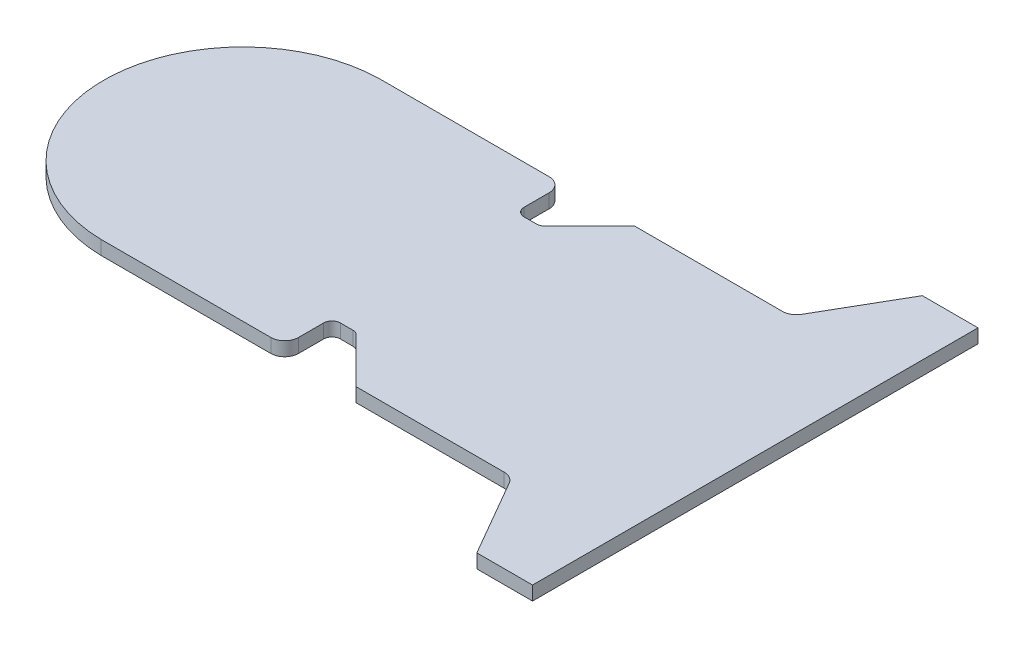
SolidWorks part; units mm, degrees
ref_plane "Front Plane" through (0, 0, 0) normal (0, 0, 1) x (1, 0, 0)
ref_plane "Top Plane" through (0, 0, 0) normal (0, 1, 0) x (1, 0, 0)
ref_plane "Right Plane" through (0, 0, 0) normal (1, 0, 0) x (0, 0, -1)
sketch "Sketch1" plane through (0, 0, 0) normal (0, 1, 0) x (1, 0, 0)
  line L0 (15.2546, 44.9902) -> (15.2546, 35.9902)
  line L1 (-50.7454, -49.9902) -> (10.2546, -49.9902)
  line L3 (-50.7454, 49.9902) -> (10.2546, 49.9902)
  line L5 (-50.7454, -49.9902) -> (50.7454, 49.9902) construction
  line L6 (-50.7454, 49.9902) -> (50.7454, -49.9902) construction
  line L7 (18.2546, 32.9902) -> (22.7119, 32.9902)
  line L8 (24.8333, 33.8689) -> (40.9546, 49.9902)
  line L9 (40.9546, 49.9902) -> (94.0678, 49.9902)
  line L10 (98.398, 52.4902) -> (114.2807, 80)
  line L11 (114.2807, 80) -> (134.2807, 80)
  line L12 (-49.7577, 0) -> (134.2807, 0) construction
  line L13 (134.2807, 80) -> (134.2807, -80)
  line L14 (40.9546, 49.9902) -> (96.9546, 49.9902)
  line L15 (40.9546, 49.9902) -> (50.7454, 49.9902)
  line L17 (114.2807, -80) -> (134.2807, -80)
  line L18 (98.398, -52.4902) -> (114.2807, -80)
  line L19 (40.9546, -49.9902) -> (94.0678, -49.9902)
  line L20 (18.2546, -32.9902) -> (22.7119, -32.9902)
  line L21 (24.8333, -33.8689) -> (40.9546, -49.9902)
  line L22 (15.2546, -44.9902) -> (15.2546, -35.9902)
  line L23 (40.9546, -49.9902) -> (50.7454, -49.9902)
  arc A0 (-50.7454, 49.9902) -> (-50.7454, -49.9902) centre (-49.7577, 0) ccw
  arc A1 (22.7119, 32.9902) -> (24.8333, 33.8689) centre (22.7119, 35.9902) ccw
  arc A2 (18.2546, 32.9902) -> (15.2546, 35.9902) centre (18.2546, 35.9902) cw
  arc A3 (15.2546, 44.9902) -> (10.2546, 49.9902) centre (10.2546, 44.9902) ccw
  arc A4 (15.2546, -44.9902) -> (10.2546, -49.9902) centre (10.2546, -44.9902) cw
  arc A5 (22.7119, -32.9902) -> (24.8333, -33.8689) centre (22.7119, -35.9902) cw
  arc A6 (18.2546, -32.9902) -> (15.2546, -35.9902) centre (18.2546, -35.9902) ccw
  arc A7 (98.398, -52.4902) -> (94.0678, -49.9902) centre (94.0678, -54.9902) ccw
  arc A8 (98.398, 52.4902) -> (94.0678, 49.9902) centre (94.0678, 54.9902) cw
  point P0 (0, 0)
  point P24 (23.9546, 32.9902)
  point P27 (15.2546, 32.9902)
  point P30 (15.2546, 49.9902)
  point P33 (15.2546, -49.9902)
  point P37 (23.9546, -32.9902)
  point P40 (15.2546, -32.9902)
  point P43 (96.9546, -49.9902)
  dimension "D2" = 100
  dimension "D11" = 3
  dimension "D12" = 5
  dimension "D13" = 5
  dimension "D14" = 3
  dimension "D15" = 5
  dimension "D1" = 120
  dimension "D3" = 8.7
  dimension "D4" = 135
  dimension "D5" = 17
  dimension "D6" = 56
  dimension "D7" = 160
  dimension "D8" = 20
  dimension "D10" = 66
extrude "Boss-Extrude1" add sketch "Sketch1" along normal blind 5 contours L3 A0 L1 L13 L11 L10 L14 L9 L8 L7 L0 region at (29.4264, 0, 0)
sketch "Sketch4" plane through (0, 5, 0) normal (0, 1, 0) x (1, 0, 0)
  line L0 (22.7119, 32.9902) -> (22.7119, -32.9902) construction
  line L1 (22.7119, 0) -> (-0.2253, 0) construction
  line L2 (22.7119, 21) -> (13.7119, 21)
  line L3 (10.7119, 18) -> (10.7119, -18)
  line L4 (13.7119, -21) -> (22.7119, -21)
  line L5 (10.7119, 21) -> (22.7119, -21) construction
  line L6 (22.7119, 21) -> (10.7119, -21) construction
  line L7 (22.7119, 21) -> (22.7119, -21)
  arc A0 (13.7119, -21) -> (10.7119, -18) centre (13.7119, -18) cw
  arc A1 (10.7119, 18) -> (13.7119, 21) centre (13.7119, 18) cw
  point P8 (16.7119, 0)
  dimension "D3" = 3
  dimension "D1" = 42
  dimension "D2" = 12
extrude "Cut-Extrude2" [suppressed] cut sketch "Sketch4" against normal through all
